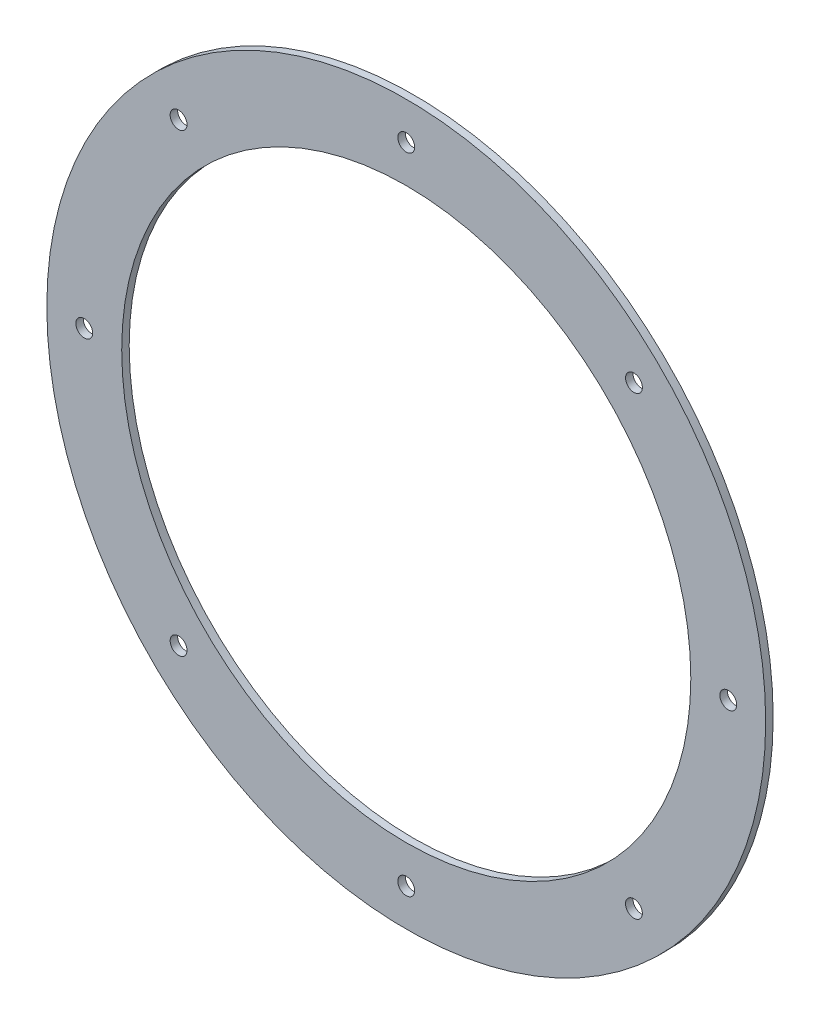
SolidWorks part; units mm, degrees
ref_plane "Front Plane" through (0, 0, 0) normal (0, 0, 1) x (1, 0, 0)
ref_plane "Top Plane" through (0, 0, 0) normal (0, 1, 0) x (1, 0, 0)
ref_plane "Right Plane" through (0, 0, 0) normal (1, 0, 0) x (0, 0, -1)
sketch "Sketch1" plane through (0, 0, 0) normal (0, 0, 1) x (1, 0, 0)
  circle A0 centre (0, 0) radius 152
  circle A1 centre (0, 0) radius 192
  dimension "D1" = 304
  dimension "D2" = 40
base flange "Base-Flange1" sketch "Sketch1" thickness 4 reverse thickness direction no parameters "D1"=0.5
sketch "Sketch2" plane through (0, 0, 0) normal (0, 0, 1) x (1, 0, 0)
  circle A0 centre (0, 0) radius 172 construction
  circle A1 centre (0, 172) radius 4.5
  circle A2 centre (0, 0) radius 192 construction
  dimension "D1" = 9
  dimension "D2" = 20
extrude "Cut-Extrude1" cut sketch "Sketch2" against normal blind 10 normal cut yes
pattern_circular "CirPattern1" count 8 over 360 about axis through (0, 0, 0) along (0, 0, 1) of "Cut-Extrude1"
sketch "Bend-Lines1" plane through (0, 0, 0) normal (0, 1, 0) x (1, 0, 0)
sketch "Bounding-Box1" plane through (0, 0, 0) normal (0, 1, 0) x (1, 0, 0)
sheet metal parameters "Sheet-Metal(1)" thickness 4 parameters "D1"=0.5
flat pattern "Flat-Pattern(1)" [suppressed]
sketch "Bend-Lines2" plane through (0, 0, 0) normal (0, 1, 0) x (1, 0, 0)
sketch "Bounding-Box2" [suppressed] plane through (0, 0, 0) normal (0, 1, 0) x (1, 0, 0)
sheet metal parameters "Sheet-Metal(2)" thickness 4 parameters "D1"=0.5
flat pattern "Flat-Pattern(1)"
sketch "Bend-Lines3" plane through (0, 0, 0) normal (0, 1, 0) x (1, 0, 0)
sketch "Bounding-Box3" [suppressed] plane through (0, 0, 0) normal (0, 1, 0) x (1, 0, 0)
sheet metal parameters "Sheet-Metal(3)" thickness 4 parameters "D1"=0.5
flat pattern "Flat-Pattern(1)"
sketch "Bend-Lines4" plane through (0, 0, 0) normal (0, 1, 0) x (1, 0, 0)
sketch "Bounding-Box4" [suppressed] plane through (0, 0, 0) normal (0, 1, 0) x (1, 0, 0)
